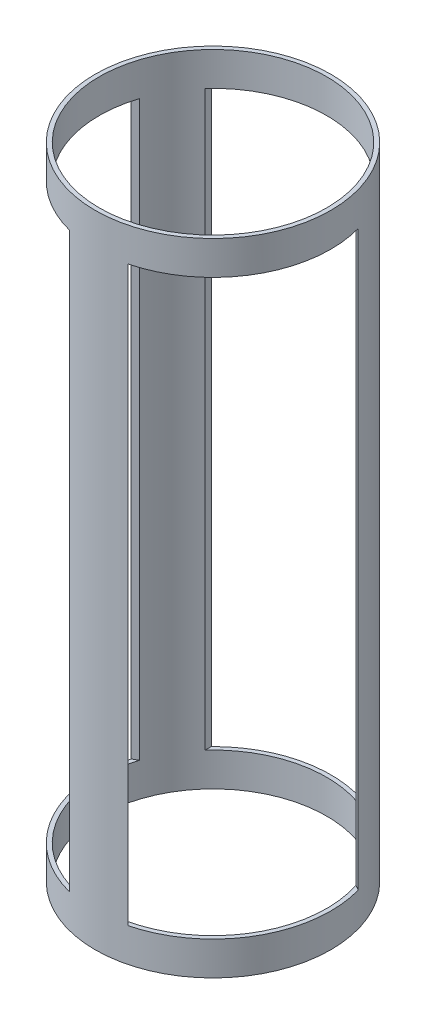
SolidWorks part; units mm, degrees
material "6061-T6 (SS)"
ref_plane "Front Plane" through (0, 0, 0) normal (0, 0, 1) x (1, 0, 0)
ref_plane "Top Plane" through (0, 0, 0) normal (0, 1, 0) x (1, 0, 0)
ref_plane "Right Plane" through (0, 0, 0) normal (1, 0, 0) x (0, 0, -1)
sketch "Sketch1" plane through (0, 0, 0) normal (0, 1, 0) x (1, 0, 0)
  circle A0 centre (0, 0) radius 88.9
  circle A1 centre (0, 0) radius 85.725
  dimension "D1" = 177.8
  dimension "D2" = 171.45
extrude "Boss-Extrude1" add sketch "Sketch1" along normal mid plane 482.854
sketch "Sketch2" plane through (0, 0, 0) normal (0, 0, 1) x (1, 0, 0)
  line L0 (85.725, 241.427) -> (-85.725, 241.427) construction
  line L1 (-63.5, -216.027) -> (63.5, -216.027)
  line L2 (-63.5, -216.027) -> (-63.5, 216.027)
  line L3 (-63.5, 216.027) -> (63.5, 216.027)
  line L4 (63.5, -216.027) -> (63.5, 216.027)
  line L5 (-63.5, -216.027) -> (63.5, 216.027) construction
  line L6 (-63.5, 216.027) -> (63.5, -216.027) construction
  line L7 (88.9, -241.427) -> (88.9, 241.427) construction
  point P0 (0, 0)
  dimension "D1" = 25.4
  dimension "D2" = 25.4
extrude "Cut-Extrude1" cut sketch "Sketch2" against normal up to surface (62.217 mm away) up to face at (0, 241.427, 88.9)
pattern_circular "CirPattern1" count 3 over 360 about axis through (0, 241.427, 0) along (0, -1, 0) of "Cut-Extrude1"
ref_plane "Plane1" through (88.9, 0, 0) normal (1, 0, 0) x (0, 0, -1)
sketch "Sketch4" plane through (88.9, 0, 0) normal (1, 0, 0) x (0, 0, -1)
  line L0 (0, 97.79) -> (0, -97.79) construction
  line L1 (88.9, 241.427) -> (-88.9, 241.427) construction
  circle A0 centre (0, 235.077) radius 1.4351
  dimension "D1" = 2.8702
  dimension "D2" = 6.35
extrude "Cut-Extrude3" [suppressed] cut sketch "Sketch4" against normal blind 15.24
pattern_circular "CirPattern3" [suppressed] count 12 over 360 of bodies 107
mirror "Mirror1" [suppressed] about plane through (0, 0, 0) normal (0, 1, 0)
ref_plane "Plane2" through (0, 0, 88.9) normal (0, 0, 1) x (1, 0, 0)
sketch "Sketch5" [suppressed] plane through (0, 0, 88.9) normal (0, 0, 1) x (1, 0, 0)
  circle A0 centre (0, 78.359) radius 1.4351
  circle A1 centre (0, -78.359) radius 1.4351
  circle A2 centre (0, -235.077) radius 1.4351 construction
  circle A3 centre (0, 235.077) radius 1.4351 construction
  dimension "D1" = 156.718
  dimension "D2" = 156.718
  dimension "D3" = 2.8702
  dimension "D4" = 2.8702
extrude "Cut-Extrude4" [suppressed] cut sketch "Sketch5" against normal blind 22.86
pattern_circular "CirPattern4" [suppressed] count 3 over 360 of bodies 110
